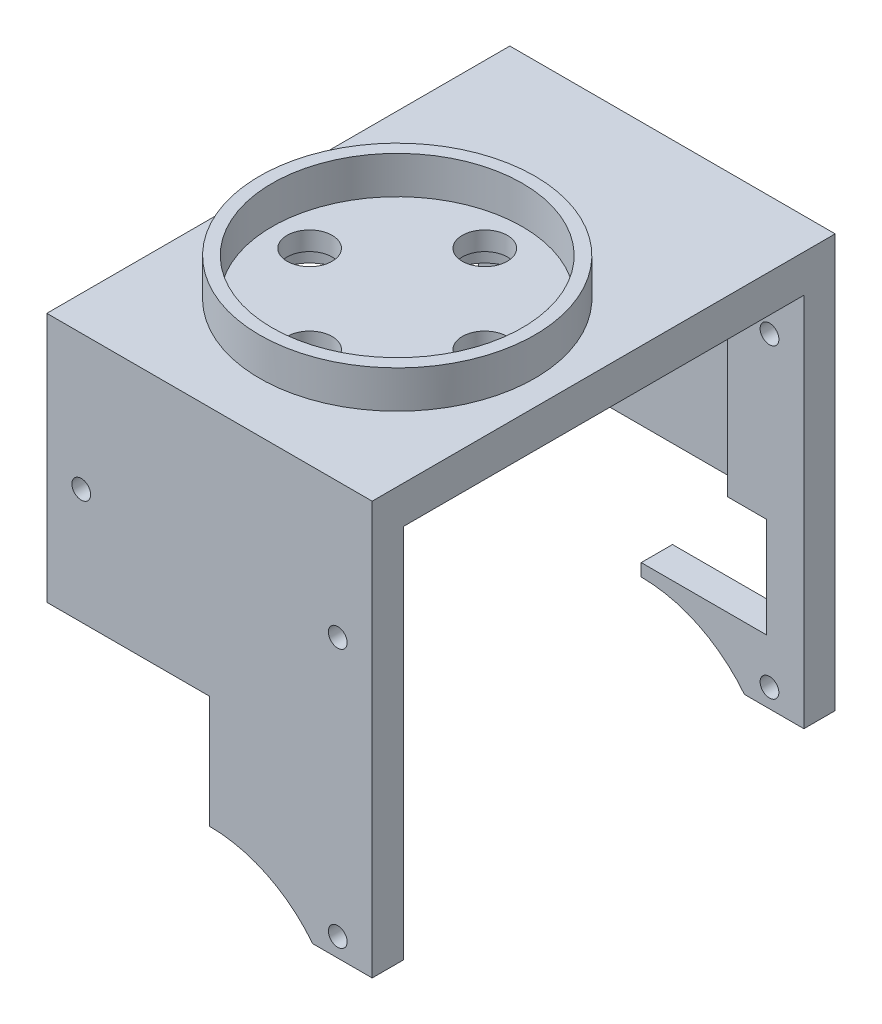
SolidWorks part; units mm, degrees
ref_plane "前视基准面" through (0, 0, 0) normal (0, 0, 1) x (1, 0, 0)
ref_plane "上视基准面" through (0, 0, 0) normal (0, 1, 0) x (1, 0, 0)
ref_plane "右视基准面" through (0, 0, 0) normal (1, 0, 0) x (0, 0, -1)
other "Configuration Table"
sketch "草图1" plane through (0, 0, 0) normal (0, 0, 1) x (1, 0, 0)
  line L1 (0, 0) -> (26, 0)
  line L2 (0, 0) -> (0, 33)
  line L3 (0, 33) -> (26, 33)
  line L4 (26, 0) -> (26, 33)
  dimension "D1" = 26
  dimension "D2" = 33
extrude "凸台-拉伸1" add sketch "草图1" along normal blind 37
sketch "草图3" plane through (0, 0, 0) normal (0, -1, 0) x (1, 0, 0)
  line L0 (0, 18.5) -> (-50000, 18.5) construction
  line L1 (0, 37) -> (0, 0) construction
  line L2 (26, 37) -> (26, 0) construction
  line L3 (0, 34.5) -> (26, 34.5)
  line L4 (0, 34.5) -> (0, 2.5)
  line L5 (0, 2.5) -> (26, 2.5)
  line L6 (26, 34.5) -> (26, 2.5)
  point P4 (0, 18.5)
  point P9 (0, 18.5)
  dimension "D1" = 32
extrude "切除-拉伸1" cut sketch "草图3" against normal offset from surface (30 mm away) 3 up to face at (13, 33, 18.5)
sketch "草图2" plane through (0, 0, 37) normal (0, 0, 1) x (1, 0, 0)
  line L0 (13, 0) -> (13, -50000) construction
  line L1 (0, 0) -> (26, 0) construction
  line L3 (2.75, 22.2) -> (23.25, 22.2) construction
  line L4 (2.75, 22.2) -> (2.75, 1.5) construction
  line L5 (2.75, 1.5) -> (23.25, 1.5) construction
  line L6 (23.25, 22.2) -> (23.25, 1.5) construction
  circle A0 centre (2.75, 1.5) radius 0.75
  circle A1 centre (23.25, 1.5) radius 0.75
  circle A2 centre (23.25, 22.2) radius 0.75
  circle A3 centre (2.75, 22.2) radius 0.75
  point P4 (13, 0)
  point P9 (13, 22.2)
  dimension "D4" = 1.5
  dimension "D5" = 1.5
  dimension "D6" = 1.5
  dimension "D7" = 1.5
  dimension "D1" = 1.5
  dimension "D2" = 20.5
  dimension "D3" = 20.7
extrude "切除-拉伸2" cut sketch "草图2" against normal up to next and the other way through all
sketch "草图4" plane through (0, 0, 0) normal (0, 0, -1) x (-1, 0, 0)
  line L1 (-23.25, 1.5) -> (-3.25, 1.5) construction
  line L2 (-23.25, 1.5) -> (-23.25, 25.95) construction
  line L3 (-23.25, 25.95) -> (-3.25, 25.95) construction
  line L4 (-3.25, 1.5) -> (-3.25, 25.95) construction
  circle A0 centre (-2.75, 1.5) radius 0.75 construction
  circle A1 centre (-23.25, 1.5) radius 0.75 construction
  circle A2 centre (-2.75, 1.5) radius 0.75
  circle A3 centre (-23.25, 1.5) radius 0.75
  circle A4 centre (-23.25, 25.95) radius 0.75
  circle A5 centre (-3.25, 25.95) radius 0.75
  dimension "D2" = 1.5
  dimension "D3" = 1.5
  dimension "D1" = 24.45
extrude "切除-拉伸3" cut sketch "草图4" against normal up to next
sketch "草图5" plane through (0, 0, 0) normal (0, -1, 0) x (1, 0, 0)
  line L0 (13, 37) -> (13, -49963) construction
  line L1 (0, 37) -> (26, 37) construction
  line L2 (0, 34.5) -> (26, 34.5) construction
  line L3 (4.5, 36) -> (21.5, 36)
  line L4 (4.5, 36) -> (4.5, 34.5)
  line L5 (4.5, 34.5) -> (21.5, 34.5)
  line L6 (21.5, 36) -> (21.5, 34.5)
  point P4 (13, 37)
  point P9 (13, 36)
  dimension "D1" = 1.5
  dimension "D2" = 17
extrude "切除-拉伸4" cut sketch "草图5" against normal blind 27
sketch "草图6" plane through (0, 0, 0) normal (0, 0, -1) x (-1, 0, 0)
  line L0 (-13, 0) -> (-13, 50000) construction
  line L1 (0, 0) -> (-26, 0) construction
  line L3 (-23, 13) -> (-3, 13)
  line L4 (-23, 13) -> (-23, 5)
  line L5 (-23, 5) -> (-3, 5)
  line L6 (-3, 13) -> (-3, 5)
  point P4 (-13, 0)
  point P9 (-13, 13)
  dimension "D1" = 5
  dimension "D2" = 8
  dimension "D3" = 20
extrude "切除-拉伸5" cut sketch "草图6" against normal up to next
sketch "草图7" plane through (0, 0, 0) normal (0, 0, -1) x (-1, 0, 0)
  line L0 (-13, 0) -> (-13, -50000) construction
  line L1 (0, 0) -> (-26, 0) construction
  line L2 (-13, 4) -> (0, 4)
  line L3 (0, 33) -> (0, 0) construction
  line L4 (-3, 13) -> (-23, 13) construction
  line L5 (-13, 4) -> (0, 4)
  line L6 (-13, 4) -> (-13, 13)
  line L7 (-13, 13) -> (0, 13)
  line L8 (0, 4) -> (0, 13)
  line L13 (0, 0) -> (0, 33)
  line L14 (0, 33) -> (-26, 33)
  line L15 (-26, 33) -> (-26, 0)
  line L16 (-26, 0) -> (0, 0)
  line L17 (0, 0) -> (0, 13)
  line L20 (-21.2462, 0) -> (0, 0)
  circle A0 centre (-13, -6.5) radius 10.5
  point P4 (-13, 0)
  line M11 (-23, 13) -> (-3, 13)
  line M12 (-3, 13) -> (-3, 5)
  line M13 (-3, 5) -> (-23, 5)
  circle M17 centre (-2.75, 1.5) radius 0.75
  line M18 (0, 0) -> (0, 33)
  line M21 (-26, 0) -> (0, 0)
  dimension "D1" = 6.5
  dimension "D2" = 21
  dimension "D3" = 0
extrude "切除-拉伸6" cut sketch "草图7" against normal through all contours L0 A0 M21 | A0 L0 L20 | A0 L20 L2 M18 M17 | L7 L6 L2 M12 M13 M18 | L6 M13 M12 M11 region at (13, 1.6294, 0) region at (3.949, 2.3453, 0) region at (12.8419, 4.5, 0) region at (8, 9, 0)
sketch "草图8" plane through (0, 13, 0) normal (0, -1, 0) x (1, 0, 0)
  line L1 (12.3977, -4.7974) -> (12.3977, 15.9697) construction
  line L3 (23, 2.5) -> (0, 2.5) construction
  line L4 (4.8977, 1) -> (19.8977, 1)
  line L5 (4.8977, 1) -> (4.8977, 2.5)
  line L6 (4.8977, 2.5) -> (19.8977, 2.5)
  line L7 (19.8977, 1) -> (19.8977, 2.5)
  point P2 (12.3977, 2.5)
  dimension "D1" = 1.5
  dimension "D2" = 15
extrude "切除-拉伸7" cut sketch "草图8" against normal blind 13
sketch "草图9" plane through (0, 33, 0) normal (0, 1, 0) x (1, 0, 0)
  line L0 (13, -37) -> (13, 49963) construction
  line L1 (26, -37) -> (0, -37) construction
  circle A0 centre (13, -22) radius 11
  circle A1 centre (13, -22) radius 10
  point P4 (13, -37)
  point P8 (13, -24.18)
  point P9 (13, -23.9135)
  dimension "D1" = 22
  dimension "D2" = 20
  dimension "D3" = 15
extrude "凸台-拉伸2" add sketch "草图9" along normal blind 3
sketch "草图10" plane through (0, 33, 0) normal (0, 1, 0) x (1, 0, 0)
  circle A0 centre (13, -22) radius 7 construction
  circle A1 centre (13, -15) radius 1.8
  circle A2 centre (20, -22) radius 1.8
  circle A3 centre (13, -29) radius 1.8
  circle A4 centre (6, -22) radius 1.8
  point P14 (13, -22)
  dimension "D1" = 14
  dimension "D2" = 3.6
  dimension "D3" = 4
extrude "切除-拉伸8" cut sketch "草图10" against normal up to next
sketch "草图11" plane through (0, 30, 0) normal (0, -1, 0) x (1, 0, 0)
  circle A0 centre (6, 22) radius 2.8
  circle A1 centre (13, 29) radius 2.8
  circle A2 centre (20, 22) radius 2.8
  circle A3 centre (13, 15) radius 2.8
  dimension "D1" = 5.6
  dimension "D2" = 5.6
  dimension "D3" = 5.6
  dimension "D4" = 5.6
extrude "切除-拉伸9" cut sketch "草图11" against normal blind 1.5
